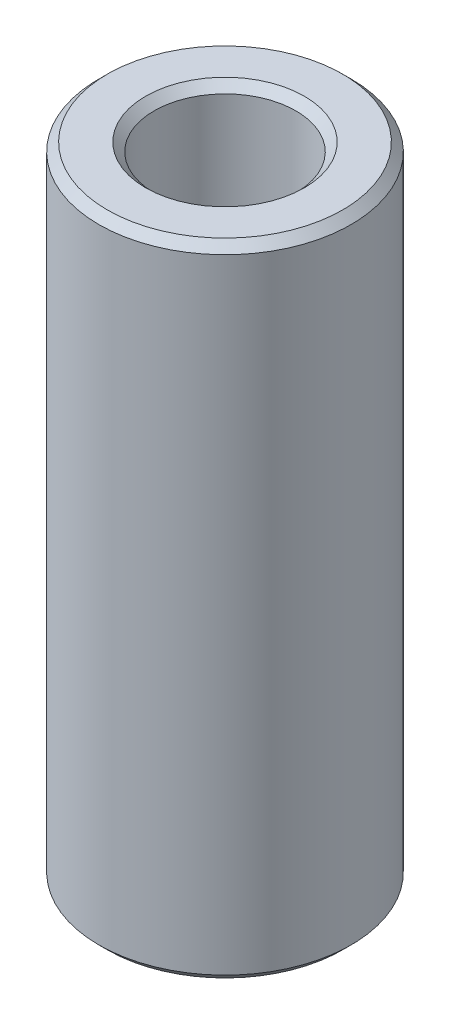
SolidWorks part; units mm, degrees
ref_plane "Front Plane" through (0, 0, 0) normal (0, 0, 1) x (1, 0, 0)
ref_plane "Top Plane" through (0, 0, 0) normal (0, 1, 0) x (1, 0, 0)
ref_plane "Right Plane" through (0, 0, 0) normal (1, 0, 0) x (0, 0, -1)
sketch "Sketch1" plane through (0, 0, 0) normal (0, 1, 0) x (1, 0, 0)
  circle A0 centre (0, 0) radius 47.5
  dimension "SLEEVE_OD" = 95
extrude "Boss-Extrude1" add sketch "Sketch1" along normal blind 241.3302
sketch "Sketch2" plane through (0, 0, 0) normal (0, 1, 0) x (1, 0, 0)
  circle A0 centre (0, 0) radius 26.7119
  dimension "BORE_D" = 53.4239
extrude "Cut-Extrude1" cut sketch "Sketch2" along normal through all
chamfer "Chamfer1" distance 3.1807 angle 45 4 edges at (0, 241.3302, 26.7119) (0, 0, 26.7119) (0, 0, 47.5) (0, 241.3302, 47.5)
